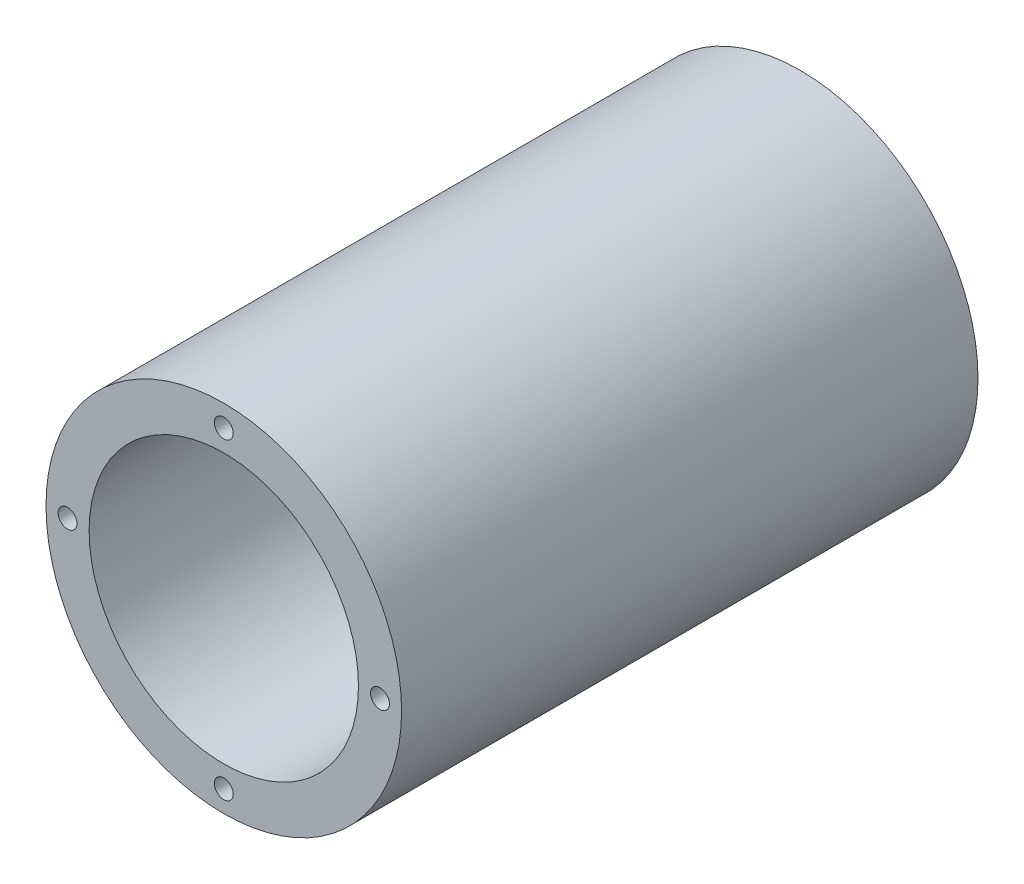
SolidWorks part; units mm, degrees
ref_plane "Alzado" through (0, 0, 0) normal (0, 0, 1) x (1, 0, 0)
ref_plane "Planta" through (0, 0, 0) normal (0, 1, 0) x (1, 0, 0)
ref_plane "Vista lateral" through (0, 0, 0) normal (1, 0, 0) x (0, 0, -1)
sketch "Croquis1" plane through (0, 0, 0) normal (0, 0, 1) x (1, 0, 0)
  circle A0 centre (0, 0) radius 33
  circle A1 centre (0, 0) radius 25
  dimension "D1" = 66
  dimension "D2" = 8
extrude "Boss-Extrude1" add sketch "Croquis1" along normal blind 107
sketch "Sketch1" plane through (0, 0, 0) normal (0, 0, -1) x (-1, 0, 0)
  line L0 (0, 0) -> (11.3818, 0) construction
  circle A0 centre (-29, 0) radius 1.5
  circle A1 centre (0, 29) radius 1.5
  circle A2 centre (29, 0) radius 1.5
  circle A3 centre (0, -29) radius 1.5
  circle A7 centre (0, 0) radius 29 construction
  circle A8 centre (0, 0) radius 25 construction
  point P17 (0, 0)
  dimension "D1" = 4
  dimension "D2" = 3
  dimension "D3" = 0
  dimension "D4" = 4
extrude "Cut-Extrude1" cut sketch "Sketch1" against normal blind 5
sketch "Sketch2" plane through (0, 0, 107) normal (0, 0, 1) x (1, 0, 0)
  circle A0 centre (-29, 0) radius 1.75
  circle A2 centre (0, 0) radius 29 construction
  circle A3 centre (0, 0) radius 25 construction
  circle A4 centre (0, 29) radius 1.75
  circle A5 centre (29, 0) radius 1.75
  circle A6 centre (0, -29) radius 1.75
  point P7 (0, 0)
  point P8 (0, 0)
  point P16 (0, 0)
  dimension "D1" = 4
  dimension "D2" = 3.5
  dimension "D3" = 4
extrude "Cut-Extrude2" cut sketch "Sketch2" against normal blind 5
